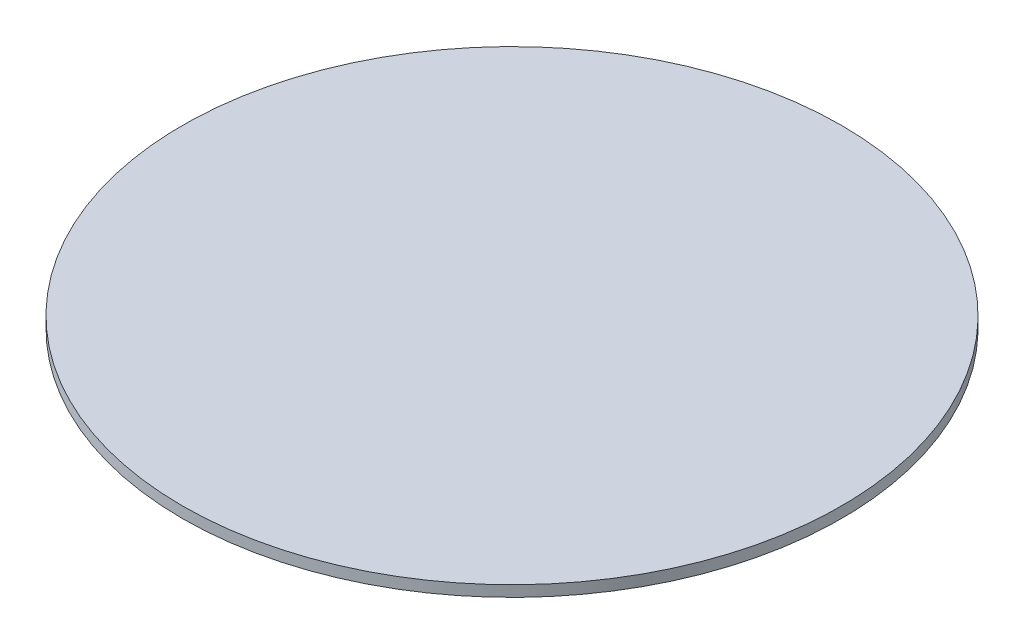
SolidWorks part; units mm, degrees
ref_plane "Front Plane" through (0, 0, 0) normal (0, 0, 1) x (1, 0, 0)
ref_plane "Top Plane" through (0, 0, 0) normal (0, 1, 0) x (1, 0, 0)
ref_plane "Right Plane" through (0, 0, 0) normal (1, 0, 0) x (0, 0, -1)
sketch "Sketch1" plane through (0, 0, 0) normal (0, 1, 0) x (1, 0, 0)
  circle A0 centre (0, 0) radius 76.2
  dimension "D1" = 152.4
extrude "Boss-Extrude1" add sketch "Sketch1" along normal blind 2.54
